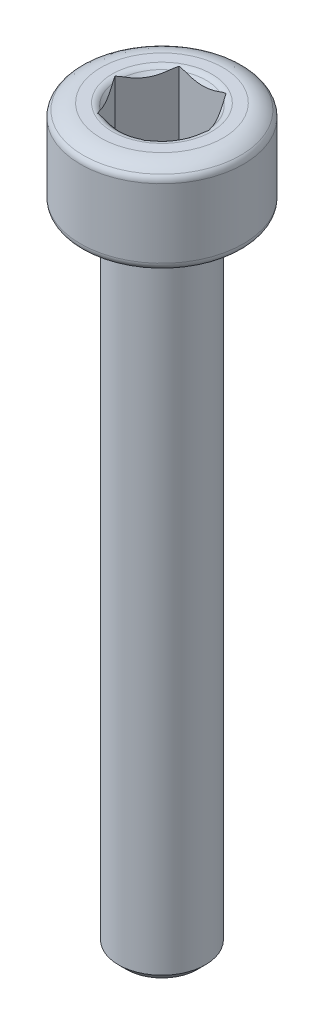
SolidWorks part; units mm, degrees
ref_plane "Front" through (0, 0, 0) normal (0, 0, 1) x (1, 0, 0)
ref_plane "Top" through (0, 0, 0) normal (0, 1, 0) x (1, 0, 0)
ref_plane "Right" through (0, 0, 0) normal (1, 0, 0) x (0, 0, -1)
sketch "Sketch1" plane through (0, 0, 0) normal (1, 0, 0) x (0, 0, -1)
  line L0 (0, 13.5) -> (0, 0) construction
  line L1 (0, 0) -> (7.1673, 0) construction
  line L2 (0, 13.5) -> (-2.498, 13.5) construction
  line L3 (0.95, 11.85) -> (1.35, 11.85)
  line L4 (0.8, 11.7) -> (0.8, 0.15)
  line L5 (0.8, 0.15) -> (0.65, 0)
  line L6 (0.65, 0) -> (0, 0)
  line L7 (0, 0) -> (0, 12)
  line L8 (1.5, 12) -> (1.5, 13.2681)
  line L9 (0.725, 13.37) -> (0.725, 12.2969)
  line L10 (0.725, 13.37) -> (0.8111, 13.4561)
  line L11 (0.875, 13.494) -> (0.875, 12.2562)
  line L12 (0.9171, 13.5) -> (1.125, 13.5)
  arc A0 (0.95, 11.85) -> (0.8, 11.7) centre (0.95, 11.7) ccw
  arc A1 (1.35, 11.85) -> (1.5, 12) centre (1.35, 12) ccw
  arc A2 (0, 12) -> (0.768, 12.1125) centre (0, 14.6781) ccw
  arc A3 (0.725, 12.2969) -> (0.5239, 12.0517) centre (0.475, 12.2969) cw
  arc A4 (0.768, 12.1125) -> (0.875, 12.2562) centre (0.725, 12.2562) ccw
  arc A5 (1.125, 13.5) -> (1.4464, 13.383) centre (1.125, 13) cw
  arc A6 (0.8111, 13.4561) -> (0.9171, 13.5) centre (0.9171, 13.35) cw
  arc A7 (1.5, 13.2681) -> (1.4464, 13.383) centre (1.35, 13.2681) ccw
  point P20 (0.725, 12.1)
  point P30 (0.855, 13.5)
  dimension "D5" = 0.15
  dimension "D11" = 0.25
  dimension "D16" = 0.5
  dimension "D1" = 1.6
  dimension "D2" = 45
  dimension "D3" = 0.15
  dimension "D4" = 11.85
  dimension "D6" = 1.65
  dimension "D7" = 1.5
  dimension "D8" = 3
  dimension "D9" = 1.45
  dimension "D10" = 0.25
  dimension "D12" = 45
  dimension "D13" = 0.13
  dimension "D14" = 2.25
  dimension "D15" = 1.75
revolve "Revolve1" add sketch "Sketch1" angle 360 about L0 region at (0, 6.6698, -0.4752)
cosmetic thread "Cosmetic Thread1" parameters "D2"=1.202
revolve "Revolve2" add sketch "Sketch1<3>" angle 360 about L0 region at (0, 12.7643, -0.7957)
sketch "Sketch1<3>" plane through (0, 0, 0) normal (1, 0, 0) x (0, 0, -1) same geometry as "Sketch1"
sketch "Sketch2" plane through (0, 11.85, 0) normal (0, -1, 0) x (1, 0, 0)
  line L1 (-0.433, 0.75) -> (-0.866, 0)
  line L2 (-0.866, 0) -> (-0.433, -0.75)
  line L3 (-0.433, -0.75) -> (0.433, -0.75)
  line L4 (0.433, -0.75) -> (0.866, 0)
  line L5 (0.866, 0) -> (0.433, 0.75)
  line L6 (0.433, 0.75) -> (-0.433, 0.75)
  circle A0 centre (0, 0) radius 0.75 construction
  dimension "D1" = 1.5
extrude "Cut-Extrude2" cut sketch "Sketch2" against normal through all
combine bodies "Combine1" operation type add bodies to combine 101 103
